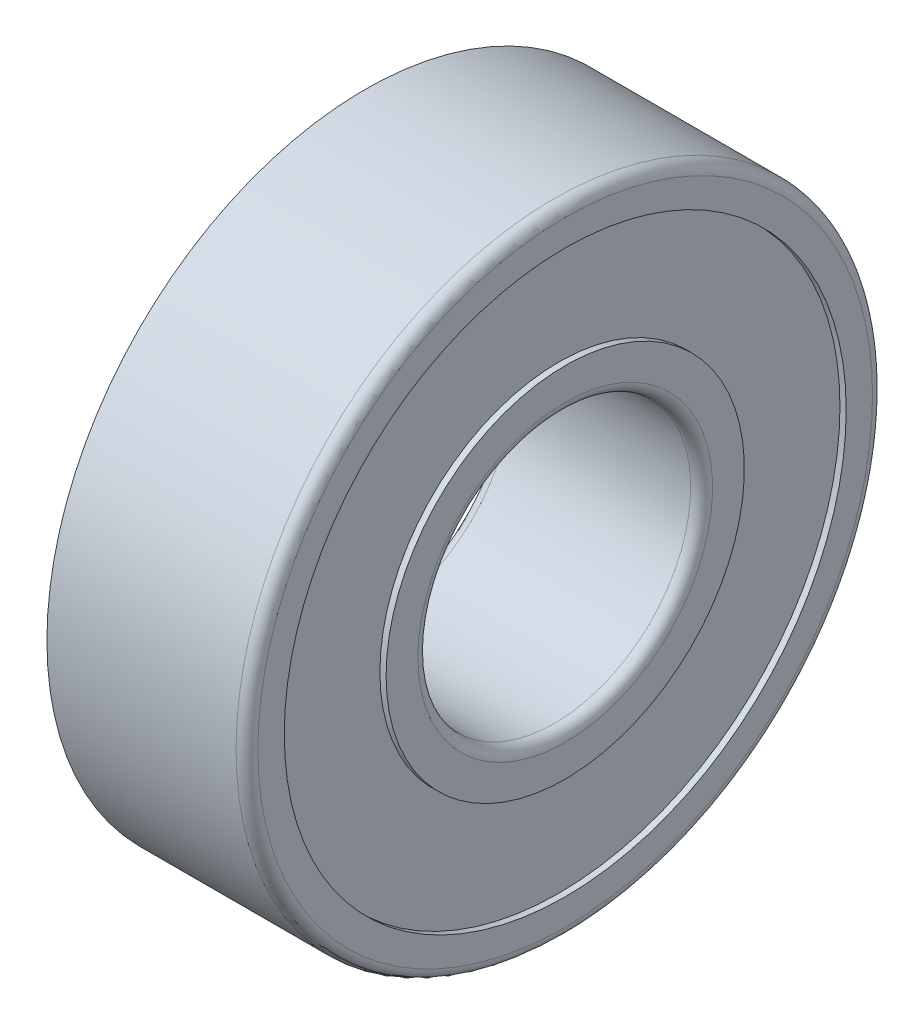
SolidWorks part; units mm, degrees
ref_plane "前视基准面" through (0, 0, 0) normal (0, 0, 1) x (1, 0, 0)
ref_plane "上视基准面" through (0, 0, 0) normal (0, 1, 0) x (1, 0, 0)
ref_plane "右视基准面" through (0, 0, 0) normal (1, 0, 0) x (0, 0, -1)
sketch "草图1" plane through (0, 0, 0) normal (0, 0, 1) x (1, 0, 0)
  line L0 (0, 17.5) -> (0, 15.45)
  line L1 (0, 15.45) -> (0.342, 15.45)
  line L2 (0.342, 15.45) -> (0.342, 9.85)
  line L3 (0.342, 9.85) -> (0, 9.85)
  line L4 (0, 9.85) -> (0, 8.1)
  line L5 (0.6, 7.5) -> (10.4, 7.5)
  line L6 (11, 8.1) -> (11, 9.85)
  line L7 (11, 9.85) -> (10.658, 9.85)
  line L8 (10.658, 9.85) -> (10.658, 15.45)
  line L9 (10.658, 15.45) -> (11, 15.45)
  line L10 (11, 15.45) -> (11, 16.9)
  line L11 (10.4, 17.5) -> (0, 17.5)
  line L12 (11, 0) -> (0, 0) construction
  arc A0 (0, 8.1) -> (0.6, 7.5) centre (0.6, 8.1) ccw
  arc A1 (10.4, 7.5) -> (11, 8.1) centre (10.4, 8.1) ccw
  arc A2 (11, 16.9) -> (10.4, 17.5) centre (10.4, 16.9) ccw
revolve "旋转1" add sketch "草图1" angle 360 about L12 reverse direction yes
ref_plane "基准面1" through (2.06, 0, 0) normal (1, 0, 0) x (0, 0, -1)
ref_plane "基准面2" through (5.5, 0, 0) normal (1, 0, 0) x (0, 0, -1)
ref_plane "to_ring XY" through (2.06, 0, 0) normal (1, 0, 0) x (0, 0, -1)
ref_plane "to_ring XZ" through (0, 0, 0) normal (0, -1, 0) x (-1, 0, 0)
ref_plane "to_ring YZ" through (0, 0, 0) normal (0, 0, -1) x (-1, 0, 0)
ref_axis "to_ring X" through (2.06, 0, 80.9) along (0, 0, -1)
ref_axis "to_ring Y" through (2.06, -50, 0) along (0, 1, 0)
ref_axis "to_ring Z" through (80.9, 0, 0) along (-1, 0, 0)
sketch3d "to_ring"
  point P0 (2.06, 0, 0)
ref_plane "to_housing XY" through (0, 0, 0) normal (1, 0, 0) x (0, 0, -1)
ref_plane "to_housing XZ" through (0, 0, 0) normal (0, -1, 0) x (-1, 0, 0)
ref_plane "to_housing YZ" through (0, 0, 0) normal (0, 0, -1) x (-1, 0, 0)
ref_axis "to_housing X" through (0, 0, 80.9) along (0, 0, -1)
ref_axis "to_housing Y" through (0, -50, 0) along (0, 1, 0)
ref_axis "to_housing Z" through (80.9, 0, 0) along (-1, 0, 0)
sketch3d "to_housing"
  point P0 (0, 0, 0)
ref_plane "center_point XY" through (5.5, 0, 0) normal (1, 0, 0) x (0, 0, -1)
ref_plane "center_point XZ" through (0, 0, 0) normal (0, -1, 0) x (-1, 0, 0)
ref_plane "center_point YZ" through (0, 0, 0) normal (0, 0, -1) x (-1, 0, 0)
ref_axis "center_point X" through (5.5, 0, 80.9) along (0, 0, -1)
ref_axis "center_point Y" through (5.5, -50, 0) along (0, 1, 0)
ref_axis "center_point Z" through (80.9, 0, 0) along (-1, 0, 0)
sketch3d "center_point"
  point P0 (5.5, 0, 0)
